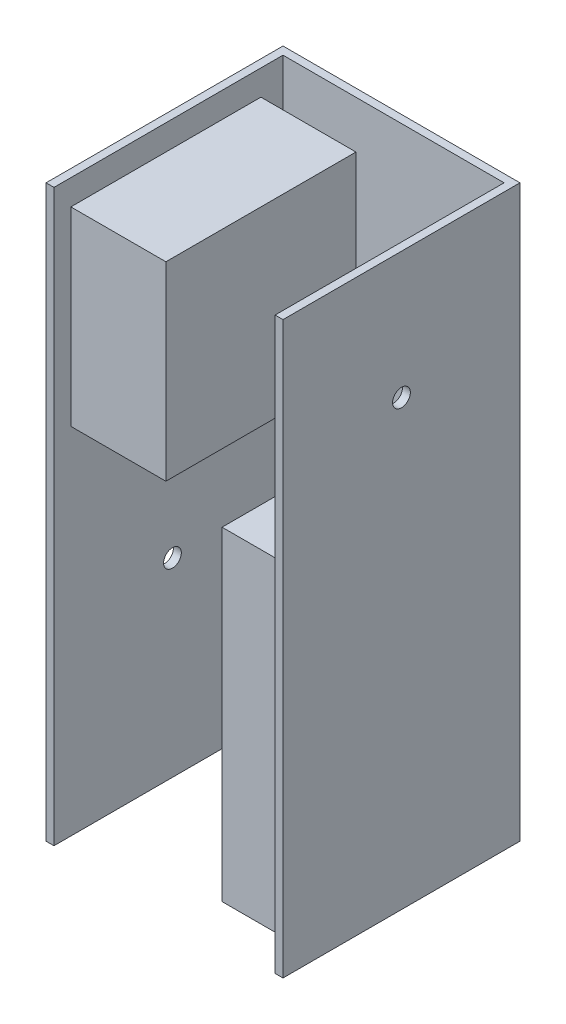
SolidWorks part; units mm, degrees
ref_plane "Front Plane" through (0, 0, 0) normal (0, 0, 1) x (1, 0, 0)
ref_plane "Top Plane" through (0, 0, 0) normal (0, 1, 0) x (1, 0, 0)
ref_plane "Right Plane" through (0, 0, 0) normal (1, 0, 0) x (0, 0, -1)
sketch "Sketch1" plane through (0, 0, 0) normal (0, 1, 0) x (1, 0, 0)
  line L1 (-23.749, 23.749) -> (23.749, 23.749)
  line L2 (-23.749, 23.749) -> (-23.749, -23.749)
  line L3 (-23.749, -23.749) -> (23.749, -23.749)
  line L4 (23.749, 23.749) -> (23.749, -23.749)
  line L5 (-22.1615, -23.749) -> (22.1615, -23.749)
  line L6 (-22.1615, -23.749) -> (-22.1615, 22.1615)
  line L7 (-22.1615, 22.1615) -> (22.1615, 22.1615)
  line L8 (22.1615, -23.749) -> (22.1615, 22.1615)
  point P4 (-23.749, 0)
  point P5 (0, -23.749)
  dimension "D1" = 47.498
  dimension "D2" = 47.498
  dimension "D3" = 1.5875
  dimension "D4" = 1.5875
  dimension "D5" = 1.5875
extrude "Boss-Extrude1" add sketch "Sketch1" along normal blind 114.3 contours L8 L3 L4 L1 L2 L6 L7 region at (0, 0, -23.0773)
sketch "Sketch3" plane through (22.1615, 0, 0) normal (-1, 0, 0) x (0, 0, 1)
  line L0 (-23.749, 0) -> (23.749, 0) construction
  line L1 (-8.3232, 70.08) -> (21.6768, 70.08)
  line L2 (-8.3232, 70.08) -> (-8.3232, 5.08)
  line L3 (-8.3232, 5.08) -> (21.6768, 5.08)
  line L4 (21.6768, 70.08) -> (21.6768, 5.08)
  dimension "D1" = 30
  dimension "D2" = 65
  dimension "D3" = 5.08
extrude "Boss-Extrude3" add sketch "Sketch3" along normal blind 12.7
sketch "Sketch5" plane through (-22.1615, 0, 0) normal (1, 0, 0) x (0, 0, -1)
  line L0 (23.749, 114.3) -> (-23.749, 114.3) construction
  line L1 (-20.3654, 109.22) -> (17.7346, 109.22)
  line L2 (-20.3654, 109.22) -> (-20.3654, 71.12)
  line L3 (-20.3654, 71.12) -> (17.7346, 71.12)
  line L4 (17.7346, 109.22) -> (17.7346, 71.12)
  dimension "D1" = 38.1
  dimension "D2" = 38.1
  dimension "D3" = 5.08
extrude "Boss-Extrude4" add sketch "Sketch5" along normal blind 19.05
sketch "Sketch8" plane through (0, 0, -23.749) normal (0, 0, -1) x (-1, 0, 0)
  line L0 (23.749, 0) -> (-23.749, 0) construction
  circle A0 centre (0, 57.15) radius 1.778
  dimension "D1" = 3.556
  dimension "D2" = 57.15
extrude "Cut-Extrude1" cut sketch "Sketch8" against normal blind 5.08
sketch "Sketch9" plane through (-23.749, 0, 0) normal (-1, 0, 0) x (0, 0, 1)
  line L0 (-23.749, 0) -> (23.749, 0) construction
  circle A0 centre (0, 38.1) radius 1.778
  dimension "D1" = 3.556
  dimension "D2" = 38.1
extrude "Cut-Extrude2" cut sketch "Sketch9" against normal blind 5.08
sketch "Sketch10" plane through (23.749, 0, 0) normal (1, 0, 0) x (0, 0, -1)
  line L0 (23.749, 114.3) -> (-23.749, 114.3) construction
  circle A0 centre (0, 88.9) radius 1.778
  dimension "D1" = 3.556
  dimension "D2" = 25.4
extrude "Cut-Extrude3" cut sketch "Sketch10" against normal blind 5.08
sketch "Sketch13" plane through (0, 0, -23.749) normal (0, 0, -1) x (-1, 0, 0)
  line L0 (23.749, 0) -> (-23.749, 0) construction
  circle A0 centre (0, 25.4) radius 1.778
  dimension "D1" = 3.556
  dimension "D2" = 25.4
extrude "Cut-Extrude6" cut sketch "Sketch13" against normal blind 5.08
